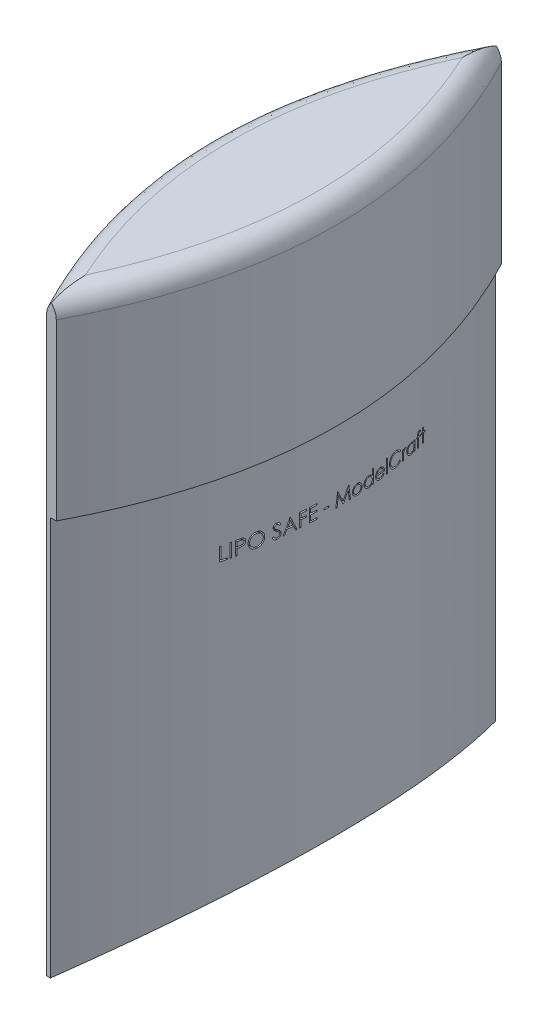
SolidWorks part; units mm, degrees
ref_plane "Plan de face" through (0, 0, 0) normal (0, 0, 1) x (1, 0, 0)
ref_plane "Plan de dessus" through (0, 0, 0) normal (0, 1, 0) x (1, 0, 0)
ref_plane "Plan de droite" through (0, 0, 0) normal (1, 0, 0) x (0, 0, -1)
sketch "Esquisse1" plane through (0, 0, 0) normal (0, 1, 0) x (1, 0, 0)
  line L0 (-0.5, 57.5) -> (-0.5, -57.5) construction
  line L1 (-19.4834, 0) -> (19.1473, 0) construction
  line L2 (0, -57.5) -> (0, 57.5) construction
  line L3 (-0.5, -57.5) -> (0.5, -57.5)
  line L4 (-0.5, 57.5) -> (0.5, 57.5)
  spline S0 degree 2 poles (-0.5, -57.5) (-30.5, 0) (-0.5, 57.5) knots 0 0 0 1 1 1
  spline S1 degree 2 poles (0.5, -57.5) (30.5, 0) (0.5, 57.5) knots 0 0 0 1 1 1
  point P5 (-15.5, 0)
  point P7 (-0.5, 0)
  dimension "D1" = 15
  dimension "D2" = 115
  dimension "D3" = 0.5
extrude "BASE" add sketch "Esquisse1" along normal blind 153
sketch "Esquisse2" plane through (0, 0, 0) normal (1, 0, 0) x (0, 0, -1)
  line L0 (0, 0) -> (0, 39.2784) construction
  line L1 (-57.5, 0) -> (57.5, 0)
  spline S0 degree 2 poles (-57.5, 0) (0, 20) (57.5, 0) knots 0 0 0 1 1 1
  point P3 (0, 10)
  point P4 (57.5, 0)
  point P5 (-57.5, 0)
  dimension "D1" = 10
extrude "BAS VIDE" cut sketch "Esquisse2" against normal through all and the other way through all
sketch "Esquisse3" plane through (0, 153, 0) normal (0, 1, 0) x (1, 0, 0)
  line L0 (0, -70.1649) -> (0, 72.6833) construction
  line L1 (0.5, -57.5) -> (2, -57.5)
  line L2 (0.5, 57.5) -> (2, 57.5)
  line L3 (15.5, 0) -> (41.0512, 0) construction
  parabola Q0 (0.5, -57.5) -> (0.5, 57.5) focus (-39.6042, 0) apex (15.5, 0) construction
  spline S0 degree 2 poles (0.5, -57.5) (30.5, 0) (0.5, 57.5) knots 0 0 0 1 1 1
  spline S1 degree 2 poles (2, -57.5) (32, 0) (2, 57.5) knots 0 0 0 1 1 1
  point P16 (17, 0)
  dimension "D1" = 1.5
  dimension "D2" = 1.5
  dimension "D3" = 1.5
extrude "LANGUETTE" add sketch "Esquisse3" against normal blind 50
fillet "LANGUETTE - CONGE" radius 5 2 edges
ref_plane "PLAN DROITE + 16 mm" through (16, 0, 0) normal (1, 0, 0) x (0, 0, -1)
sketch "Esquisse4" plane through (16, 0, 0) normal (1, 0, 0) x (0, 0, -1)
  text T0 "LIPO SAFE - ModelCraft"
extrude "GRAVURE-NOM" cut sketch "Esquisse4" against normal blind 5
